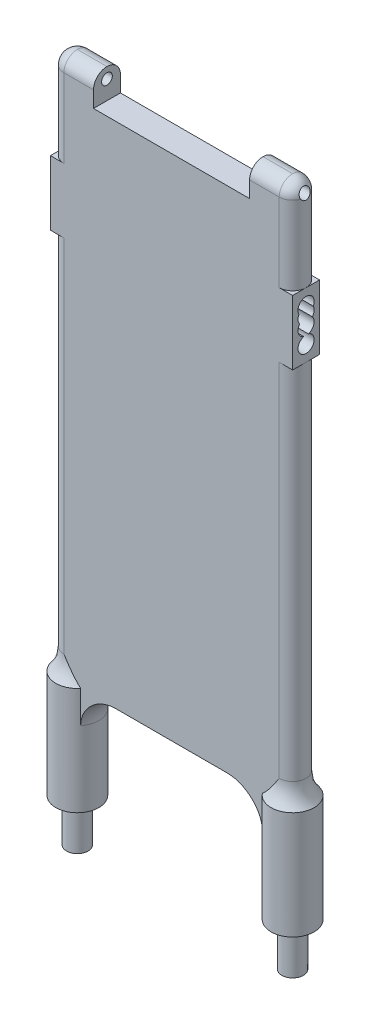
SolidWorks part; units mm, degrees
note: The reader was unsure of these and kept them because the rebuilt part matched: shared geometry of "Sketch1<3>".
ref_plane "Front Plane" through (0, 0, 0) normal (0, 0, 1) x (1, 0, 0)
ref_plane "Top Plane" through (0, 0, 0) normal (0, 1, 0) x (1, 0, 0)
ref_plane "Right Plane" through (0, 0, 0) normal (1, 0, 0) x (0, 0, -1)
sketch "Sketch1" plane through (0, 0, 0) normal (0, 1, 0) x (1, 0, 0)
  line L0 (-20, 0) -> (20, 0) construction
  circle A0 centre (-20, 0) radius 2
  circle A1 centre (20, 0) radius 2
  circle A2 centre (-20, 0) radius 4
  circle A3 centre (20, 0) radius 4
  point P8 (0, 0)
  dimension "D2" = 4
  dimension "D1" = 40
  dimension "D3" = 2
extrude "Boss-Extrude1" add sketch "Sketch1" against normal blind 8
extrude "Boss-Extrude2" add sketch "Sketch1<3>" along normal blind 20
sketch "Sketch1<3>" plane through (0, 0, 0) normal (0, 1, 0) x (1, 0, 0) same geometry as "Sketch1"
sketch "Sketch2" plane through (0, 20, 0) normal (0, 1, 0) x (1, 0, 0)
  line L0 (-20, 0) -> (20, 0) construction
  line L1 (-20, 2.5) -> (20, 2.5)
  line L2 (-20, -2.5) -> (20, -2.5)
  arc A0 (-20, 2.5) -> (-20, -2.5) centre (-20, 0) ccw
  arc A1 (20, -2.5) -> (20, 2.5) centre (20, 0) ccw
  point P4 (0, 0)
  dimension "D1" = 5
extrude "Boss-Extrude3" add sketch "Sketch2" along normal blind 100
fillet "Fillet1" radius 6 2 edges at (-16, 20, 0) (16, 20, 0)
fillet "Fillet2" radius 6 2 edges at (-22.5, 20, 0) (22.5, 20, 0)
sketch "Sketch3" plane through (0, 0, 2.5) normal (0, 0, 1) x (1, 0, 0)
  line L0 (-20, 120) -> (20, 120) construction
  line L1 (-14.5, 120) -> (14.5, 120)
  line L2 (-14.5, 120) -> (-14.5, 114.5)
  line L3 (-14.5, 114.5) -> (14.5, 114.5)
  line L4 (14.5, 120) -> (14.5, 114.5)
  dimension "D1" = 5.5
  dimension "D2" = 8
  dimension "D3" = 8
extrude "Cut-Extrude1" cut sketch "Sketch3" against normal mid plane 10
sketch "Sketch4" plane through (14.5, 0, 0) normal (-1, 0, 0) x (0, 0, 1)
  line L0 (2.5, 120) -> (-2.5, 120) construction
  circle A0 centre (0, 118) radius 1
  point P4 (0, 120)
  dimension "D1" = 2
  dimension "D2" = 2
extrude "Cut-Extrude2" cut sketch "Sketch4" against normal through all both and the other way through all
fillet "Fillet3" radius 2.5 6 edges at (17.25, 120, 2.5) (17.25, 120, -2.5) (-17.25, 120, -2.5) (-17.25, 120, 2.5) (22.5, 120, 0) (-22.5, 120, 0)
ref_plane "Plane1" through (-20, 0, 0) normal (1, 0, 0) x (0, -1, 0)
sketch "Sketch5" plane through (-20, 0, 0) normal (1, 0, 0) x (0, -1, 0)
  line L0 (-117.5, 0) -> (-23.9686, 0) construction
  circle A0 centre (-100, 0) radius 1.5
  arc A1 (-117.5, -0.866) -> (-117.5, 0.866) centre (-118, 0) ccw construction
  circle A3 centre (-98.59, 0) radius 1.5
  circle A4 centre (-96.71, 0) radius 1.5
  circle A5 centre (-93.83, 0) radius 1.5
  dimension "D1" = 3
  dimension "D2" = 18
  dimension "D5" = 19.41
  dimension "D6" = 21.29
  dimension "D7" = 24.17
extrude "Cut-Extrude3" cut sketch "Sketch5" against normal blind 3 and the other way blind 6
ref_plane "Plane2" through (-20, 0, 0) normal (-1, 0, 0) x (0, 0, 1)
sketch "Sketch6" plane through (-20, 0, 0) normal (-1, 0, 0) x (0, 0, 1)
  line L0 (0, 101.5) -> (0, 92.33) construction
  line L1 (-2.5, 102.915) -> (2.5, 102.915)
  line L2 (-2.5, 102.915) -> (-2.5, 90.915)
  line L3 (-2.5, 90.915) -> (2.5, 90.915)
  line L4 (2.5, 102.915) -> (2.5, 90.915)
  line L5 (-2.5, 102.915) -> (2.5, 90.915) construction
  line L6 (-2.5, 90.915) -> (2.5, 102.915) construction
  line L7 (-2.5, 117.5) -> (-2.5, 23.9686) construction
  arc A0 (1.1689, 97.65) -> (1.324, 99.295) centre (0, 98.59) ccw construction
  arc A1 (0.42, 95.27) -> (1.1689, 97.65) centre (0, 96.71) ccw construction
  arc A2 (-1.1689, 97.65) -> (-0.42, 95.27) centre (0, 96.71) ccw construction
  arc A3 (-1.324, 99.295) -> (-1.1689, 97.65) centre (0, 98.59) ccw construction
  arc A4 (-0.42, 95.27) -> (0.42, 95.27) centre (0, 93.83) ccw construction
  arc A5 (1.324, 99.295) -> (-1.324, 99.295) centre (0, 100) ccw construction
  arc A6 (1.1689, 97.65) -> (1.324, 99.295) centre (0, 98.59) ccw
  arc A7 (0.42, 95.27) -> (1.1689, 97.65) centre (0, 96.71) ccw
  arc A8 (-1.1689, 97.65) -> (-0.42, 95.27) centre (0, 96.71) ccw
  arc A9 (-1.324, 99.295) -> (-1.1689, 97.65) centre (0, 98.59) ccw
  arc A10 (-0.42, 95.27) -> (0.42, 95.27) centre (0, 93.83) ccw
  arc A11 (1.324, 99.295) -> (-1.324, 99.295) centre (0, 100) ccw
  point P5 (0, 96.915)
  point P17 (0, 96.915)
  dimension "D2" = 12
extrude "Boss-Extrude4" add sketch "Sketch6" along normal blind 2.5
mirror "Mirror1" about plane through (0, 0, 0) normal (1, 0, 0) of "Boss-Extrude4", "Cut-Extrude3"
